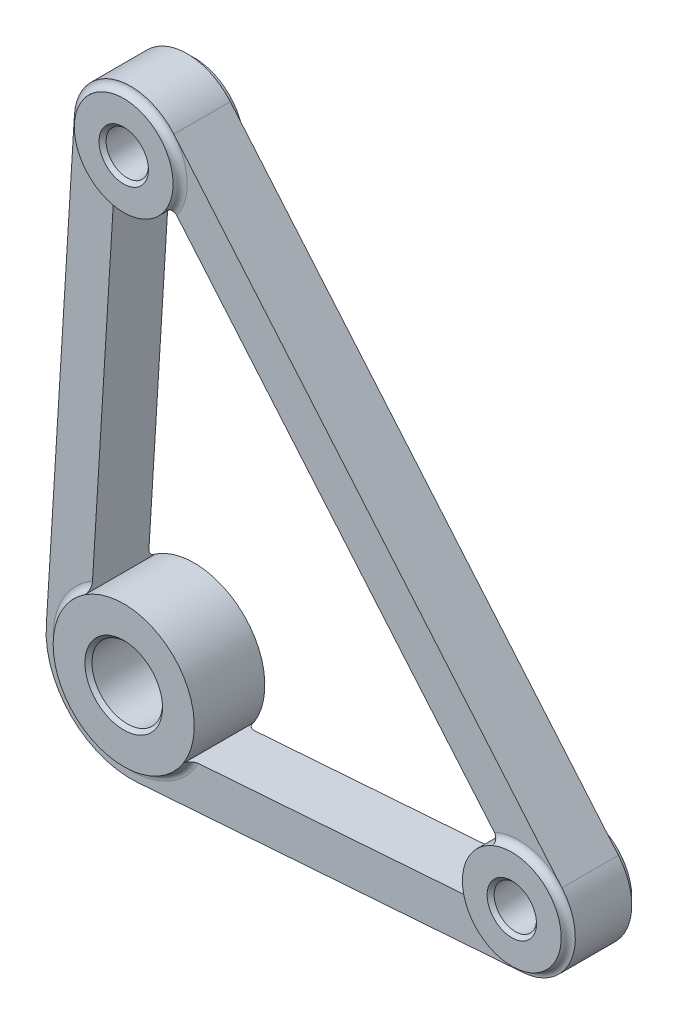
SolidWorks part; units mm, degrees
ref_plane "Front Plane" through (0, 0, 0) normal (0, 0, 1) x (1, 0, 0)
ref_plane "Top Plane" through (0, 0, 0) normal (0, 1, 0) x (1, 0, 0)
ref_plane "Right Plane" through (0, 0, 0) normal (1, 0, 0) x (0, 0, -1)
sketch "Sketch1" plane through (0, 0, 0) normal (0, 0, 1) x (1, 0, 0)
  line L0 (-11.9773, 0.7385) -> (-7.9848, 65.4923)
  line L1 (6.1071, 70.1675) -> (61.1071, 5.1675)
  line L2 (55.5818, -7.9788) -> (0.8727, -11.9682)
  arc A0 (-11.9773, 0.7385) -> (0.8727, -11.9682) centre (0, 0) ccw
  arc A1 (6.1071, 70.1675) -> (-7.9848, 65.4923) centre (0, 65) ccw
  arc A2 (55.5818, -7.9788) -> (61.1071, 5.1675) centre (55, 0) ccw
  point P13 (0, 0)
  point P14 (0, 0)
  dimension "D1" = 24
  dimension "D2" = 16
  dimension "D3" = 16
  dimension "D5" = 55
  dimension "D4" = 65
extrude "Boss-Extrude1" add sketch "Sketch1" along normal mid plane 8
sketch "Sketch2" plane through (0, 0, 4) normal (0, 0, 1) x (1, 0, 0)
  circle A0 centre (0, 0) radius 10
  circle A1 centre (0, 65) radius 7
  circle A2 centre (55, 0) radius 7
  point P7 (0, 0)
  point P8 (0, 0)
  dimension "D1" = 20
  dimension "D2" = 14
  dimension "D3" = 14
  dimension "D5" = 65
  dimension "D4" = 55
extrude "Boss-Extrude2" add sketch "Sketch2" along normal mid plane 2
mirror "Mirror4" about plane through (0, 0, 0) normal (0, 0, 1) of "Boss-Extrude2"
sketch "Sketch4" plane through (0, 0, 0) normal (0, 0, 1) x (1, 0, 0)
  line L46 (0.4364, -5.9841) -> (55.1455, -1.9947)
  line L47 (56.5268, 1.2919) -> (1.5268, 66.2919)
  line L48 (-1.9962, 65.1231) -> (-5.9886, 0.3692)
  line L49 (0.4364, -5.9841) -> (55.1455, -1.9947)
  line L50 (56.5268, 1.2919) -> (1.5268, 66.2919)
  line L51 (-1.9962, 65.1231) -> (-5.9886, 0.3692)
  arc A20 (-5.9886, 0.3692) -> (0.4364, -5.9841) centre (0, 0) ccw
  arc A21 (55.1455, -1.9947) -> (56.5268, 1.2919) centre (55, 0) ccw
  arc A22 (1.5268, 66.2919) -> (-1.9962, 65.1231) centre (0, 65) ccw
  arc A23 (-5.9886, 0.3692) -> (0.4364, -5.9841) centre (0, 0) ccw
  arc A24 (55.1455, -1.9947) -> (56.5268, 1.2919) centre (55, 0) ccw
  arc A25 (1.5268, 66.2919) -> (-1.9962, 65.1231) centre (0, 65) ccw
  dimension "D1" = 6
extrude "Cut-Extrude1" cut sketch "Sketch4" against normal through all both and the other way through all contours A23 L49 A24 L50 A25 L51
fillet "Fillet4" radius 1 18 edges at (51.8002, -2.2386, 5) (54.3602, 3.8524, 5) (51.8002, -2.2386, -5) (54.3602, 3.8524, -5) (-2.2026, 61.7753, 5) (-2.2026, 61.7753, -5) (-4.2188, -4.2664, 5) (-4.2188, -4.2664, -5) (56.8438, -0.7749, 5) (56.8438, -0.7749, -5) (-0.6298, 66.8983, 5) (-0.6298, 66.8983, -5) (-5.7425, 4.3616, 5) (4.4258, -5.6932, 5) (-5.7425, 4.3616, -5) (4.4258, -5.6932, -5) (3.6933, 63.7314, 5) (3.6933, 63.7314, -5)
sketch "Sketch5" plane through (0, 0, 4) normal (0, 0, 1) x (1, 0, 0)
  circle A0 centre (0, 0) radius 5
  circle A1 centre (55, 0) radius 3
  circle A2 centre (0, 65) radius 3
  dimension "D1" = 10
  dimension "D2" = 6
  dimension "D3" = 6
sketch "Sketch7" plane through (0, 0, 5) normal (0, 0, 1) x (1, 0, 0)
  circle A10 centre (0, 65) radius 7
  circle A11 centre (0, 0) radius 10
  circle A12 centre (55, 0) radius 7
  dimension "D1" = 20
  dimension "D2" = 14
  dimension "D3" = 14
extrude "Boss-Extrude4" add sketch "Sketch7" against normal up to surface (10 mm away) up to face at (-0.5012, 66.5109, -5)
extrude "Cut-Extrude2" cut sketch "Sketch5" against normal through all both and the other way through all
fillet "Fillet5" radius 1 6 edges at (-2.2042, 71.6439, -4) (-7.0313, -7.1106, -4) (61.4532, -2.7122, -4) (61.4532, -2.7122, 4) (-7.0313, -7.1106, 4) (-2.2042, 71.6439, 4)
chamfer "Chamfer1" distance 0.5 angle 45 6 edges at (3, 65, -5) (5, 0, -5) (58, 0, -5) (58, 0, 5) (5, 0, 5) (3, 65, 5)
